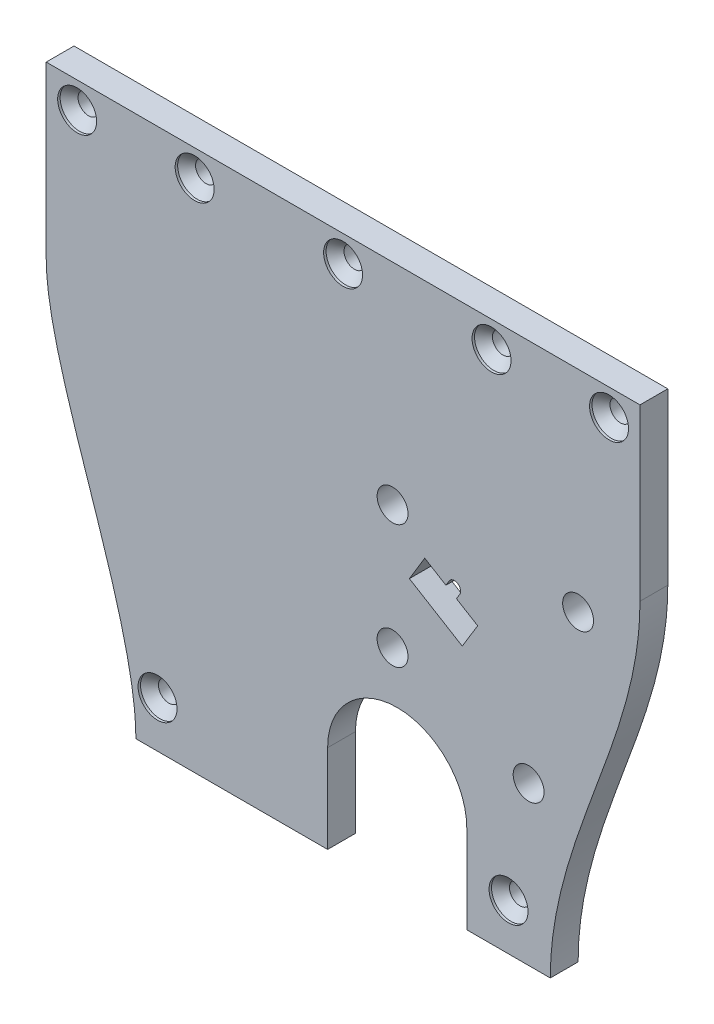
SolidWorks part; units mm, degrees
ref_plane "Front Plane" through (0, 0, 0) normal (0, 0, 1) x (1, 0, 0)
ref_plane "Top Plane" through (0, 0, 0) normal (0, 1, 0) x (1, 0, 0)
ref_plane "Right Plane" through (0, 0, 0) normal (1, 0, 0) x (0, 0, -1)
sketch "Sketch1" plane through (0, 0, 0) normal (0, 0, 1) x (1, 0, 0)
  line L0 (-96, 87.5) -> (0, 87.5)
  line L1 (-96, 87.5) -> (-96, 60) construction
  line L2 (0, 60) -> (0, 87.5) construction
  line L3 (-96, 87.5) -> (-96, 60)
  line L4 (0, 60) -> (0, 87.5)
  line L5 (-81.5, 0) -> (-50.5, 0)
  line L8 (-50.5, 14.25) -> (-50.5, 0)
  line L9 (-28, 14.25) -> (-28, 0)
  line L10 (-28, 0) -> (-14.5, 0) construction
  line L11 (-28, 0) -> (-14.5, 0)
  arc A0 (-28, 14.25) -> (-50.5, 14.25) centre (-39.25, 14.25) ccw
  circle A1 centre (-91, 83.25) radius 1.5
  circle A2 centre (-72, 83.25) radius 1.5
  circle A3 centre (-48, 83.25) radius 1.5
  circle A4 centre (-5, 83.25) radius 1.5
  circle A5 centre (-24, 83.25) radius 1.5
  circle A6 centre (-21.25, 7.5) radius 1.5
  circle A7 centre (-78, 7.5) radius 1.5
  spline S0 degree 3 poles (758.7403, -459.0464) (-1035.6768, 781.853) (866.7995, -708.7239) (-959.7206, 478.239) knots -2.661345 -2.661345 -2.661345 -2.661345 3.688798 3.688798 3.688798 3.688798 only from (-96, 60) to (-81.5, 0) construction
  spline S1 degree 3 poles (-926.4822, 436.3245) (70.4103, 143.3489) (-40.5796, 39.2803) (-23.296, -115.324) (977.5002, -126.213) knots -2.74375 -2.74375 -2.74375 -2.74375 0.602811 3.81543 3.81543 3.81543 3.81543 only from (0, 60) to (-14.5, 0) construction
  spline S2 degree 3 poles (-96, 60) (-96, 44.4793) (-81.5, 17.4381) (-81.5, 0) knots 0 0 0 0 1 1 1 1
  spline S3 degree 3 poles (0, 60) (0, 47.4409) (-8.7408, 28.352) (-14.5, 8.0884) (-14.5, 0) knots 0 0 0 0 0.602811 1 1 1 1
  dimension "D1" = 22.5
  dimension "D2" = 3
extrude "Boss-Extrude1" add sketch "Sketch1" along normal blind 4.5
sketch "Sketch2" plane through (0, 0, 4.5) normal (0, 0, 1) x (1, 0, 0)
  line L0 (0, 87.5) -> (-96, 87.5) construction
  line L1 (0, 60) -> (0, 87.5) construction
  line L2 (-10, 53.5) -> (-40, 53.5) construction
  line L3 (-40, 53.5) -> (-40, 33.5) construction
  line L4 (-40, 33.5) -> (-37.5, 33.5) construction
  line L7 (-10.1117, 51.0025) -> (-10, 53.5) construction
  circle A0 centre (-10, 53.5) radius 2.5
  circle A1 centre (-40, 53.5) radius 2.5
  circle A2 centre (-40, 33.5) radius 2.5
  circle A3 centre (-18, 25.5) radius 2.5
  dimension "D1" = 5
  dimension "D2" = 34
  dimension "D3" = 10
  dimension "D4" = 30
  dimension "D5" = 20
  dimension "D6" = 8
  dimension "D7" = 22
extrude "Cut-Extrude1" cut sketch "Sketch2" against normal through all
sketch "Sketch3" plane through (0, 0, 4.5) normal (0, 0, 1) x (1, 0, 0)
  circle A0 centre (-30.0011, 46.8996) radius 1
  point P3 (0, 0)
extrude "Cut-Extrude2" cut sketch "Sketch3" against normal through all
sketch "Sketch4" plane through (0, 0, 0) normal (0, 0, -1) x (-1, 0, 0)
  line L0 (28.7284, 39.3484) -> (37.2823, 44.5281)
  line L1 (28.7284, 39.3484) -> (26.2421, 43.4543)
  line L2 (37.2823, 44.5281) -> (34.7961, 48.634)
  line L3 (26.2421, 43.4543) -> (29.6644, 45.5266)
  line L4 (30.0011, 46.8996) -> (46.9486, 18.9117) construction
  line L5 (29.1259, 46.4159) -> (29.6644, 45.5266)
  line L6 (30.8565, 47.4175) -> (31.3745, 46.5621)
  line L7 (31.3745, 46.5621) -> (34.7961, 48.634)
  circle A0 centre (39.25, 14.25) radius 9 construction
  circle A1 centre (30.0011, 46.8996) radius 1 construction
  arc A2 (30.8565, 47.4175) -> (29.1259, 46.4159) centre (30.0011, 46.8996) ccw
  point P14 (33.0053, 41.9382)
  dimension "D1" = 18
  dimension "D2" = 10
  dimension "D3" = 4.8
extrude "Cut-Extrude3" cut sketch "Sketch4" against normal through all
hole_wizard "CSK for M3 Countersunk Flat Head Screw1" positions "Sketch5" profile "Sketch6" countersink size "M3" standard "ISO" end condition through all
sketch "Sketch5" plane through (0, 0, 4.5) normal (0, 0, 1) x (1, 0, 0)
  point P0 (-91, 83.25)
  point P3 (-72, 83.25)
  point P6 (-48, 83.25)
  point P9 (-24, 83.25)
  point P12 (-5, 83.25)
  point P15 (-21.25, 7.5)
  point P18 (-78, 7.5)
sketch "Sketch6" plane through (-91, 83.25, 4.5) normal (1, 0, 0) x (0, -1, 0)
  line L0 (0, 0) -> (0, 4.5)
  line L1 (0, 4.5) -> (1.7, 4.5)
  line L2 (1.7, 4.5) -> (1.7, 1.85)
  line L3 (1.7, 1.85) -> (3.15, 0.4)
  line L4 (3.15, 0.4) -> (3.15, 0)
  line L6 (3.15, 0) -> (0, 0)
  line L7 (-1.7, 1.85) -> (-3.15, 0.4) construction
  line L11 (0, -6.35) -> (0, 107.95) construction
  dimension "Thru Hole Dia." = 3.4
  dimension "Thru Hole Depth" = 4.5
  dimension "C'Sink Dia." = 6.3
  dimension "C'Sink Angle" = 90
  dimension "Head Clearance" = 0.4
